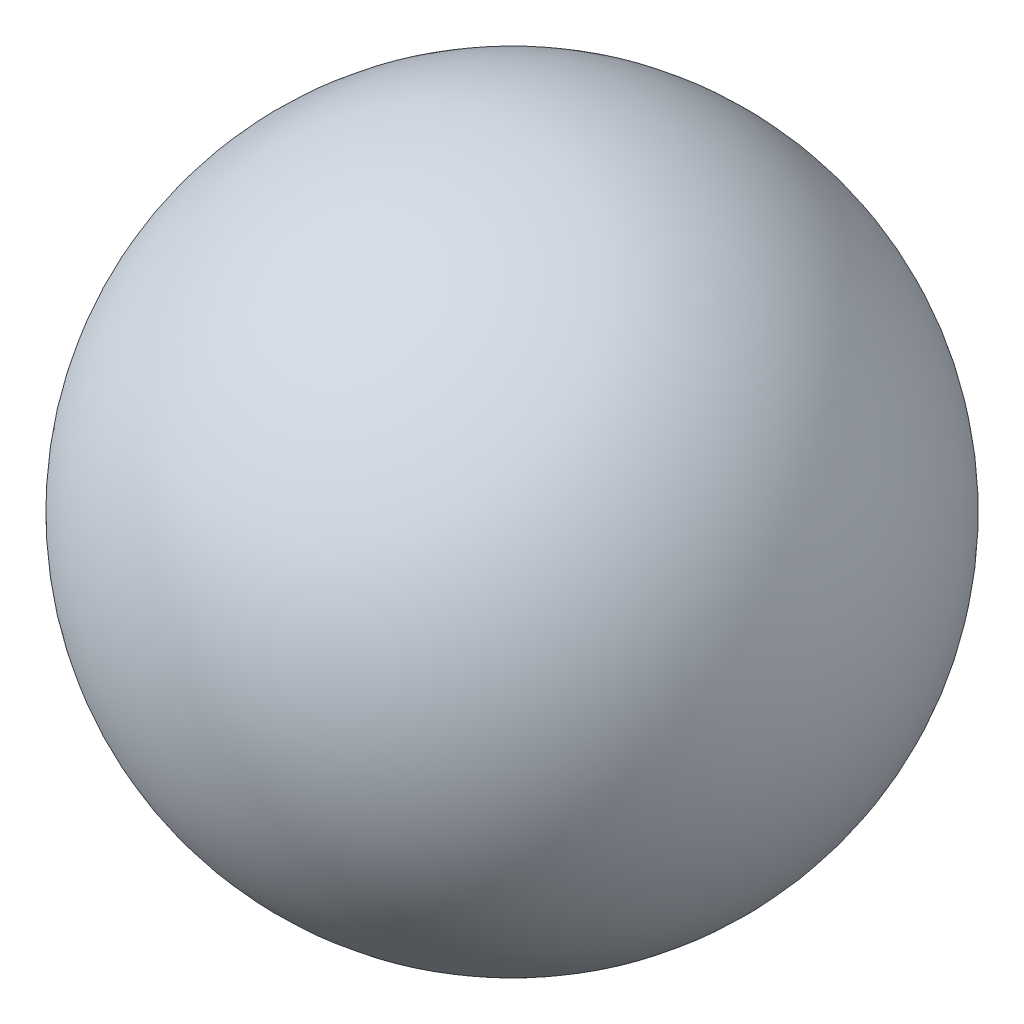
SolidWorks part; units mm, degrees
material "ｼﾘｺﾝ ｺﾞﾑ"
ref_plane "正面" through (0, 0, 0) normal (0, 0, 1) x (1, 0, 0)
ref_plane "平面" through (0, 0, 0) normal (0, 1, 0) x (1, 0, 0)
ref_plane "右側面" through (0, 0, 0) normal (1, 0, 0) x (0, 0, -1)
sketch "ｽｹｯﾁ1" plane through (0, 0, 0) normal (0, 0, 1) x (1, 0, 0)
  line L0 (0, -12.65) -> (0, 12.65) construction
  line L1 (0, 115) -> (0, -115)
  arc A0 (0, 115) -> (0, -115) centre (0, 0) cw
  dimension "D1" = 230
revolve "回転1" add sketch "ｽｹｯﾁ1" angle 360 about L1 region at (48.8075, 0, 0)
